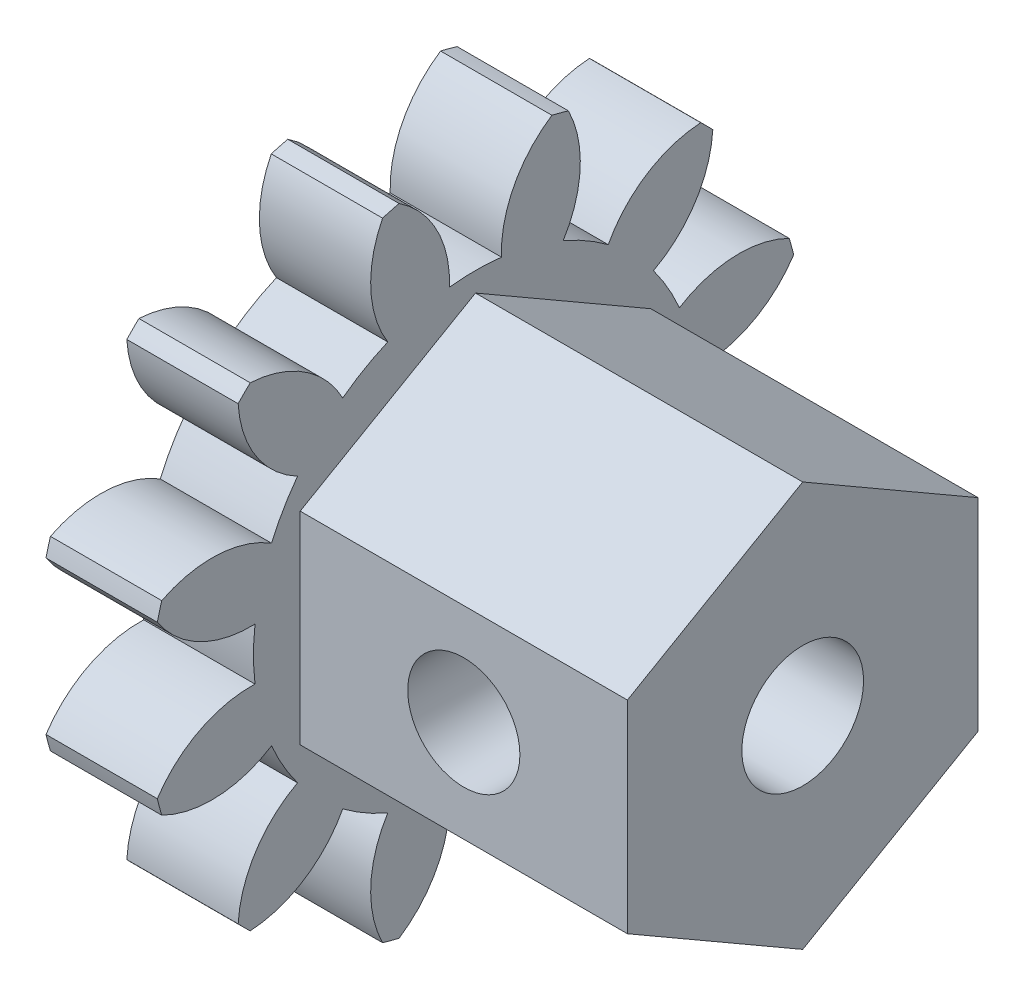
SolidWorks part; units mm, degrees
ref_plane "Plane1" through (0, 0, 0) normal (0, 0, 1) x (1, 0, 0)
ref_plane "Plane2" through (0, 0, 0) normal (0, 1, 0) x (1, 0, 0)
ref_plane "Plane3" through (0, 0, 0) normal (1, 0, 0) x (0, 0, -1)
sketch "HoldingSke" plane through (0, 0, 0) normal (0, 1, 0) x (1, 0, 0)
  line L0 (0, 0) -> (0.4891, -0.104)
  line L1 (-15, 0) -> (100, 0) construction
  line L2 (0, 0) -> (-2.1039, 2.3779)
  line L3 (0, 0) -> (-11.863, 4.5341)
  line L4 (0, 0) -> (8.4473, 1.7955)
  line L5 (0, 0) -> (-46.8476, -17.4728)
  line L6 (0, 0) -> (-3.9479, -2.6637)
  line L7 (-2.1039, 2.3779) -> (8.6586, 51.2059)
  line L8 (-76.2, 54.61) -> (-74.4, 54.61)
  line L9 (-71.009, 38.7566) -> (-53.1078, 45.2721)
  line L10 (-76.2, 71.12) -> (104.1128, 71.12)
  line L11 (0, 0) -> (-4.7625, 0)
  line L12 (-76.2, 101.6) -> (-76.133, 101.6)
  line L13 (24.9733, 27.94) -> (52.9518, 28.4284)
  line L14 (24.9733, 27.94) -> (24.9743, 27.94)
  line L15 (24.9733, 27.94) -> (100.4006, 29.5858)
  line L16 (-63.627, -2) -> (-12.827, -2)
  circle A0 centre (0, 0) radius 5
  circle A1 centre (0, 0) radius 9.499
  circle A2 centre (0, 0) radius 37.5
  circle A3 centre (0, 0) radius 5
  dimension "MHD" = 18.998
  dimension "Hub_dia" = 75
  dimension "Bore" = 10
  dimension "MBD" = 10
  dimension "Num_teeth" = 12
  dimension "Pitch_radius" = 180.3128
  dimension "Pitch" = 0.5
  dimension "Width" = 4.7625
  dimension "Overall_len" = 50
  dimension "Show_teeth" = 12
  dimension "Thickness" = 4.7625
  dimension "OAL" = 50.0001
  dimension "T_dim" = 1.8
  dimension "Ap" = 20
  dimension "H" = 19.05
  dimension "Backlash" = 0.067
  dimension "Addendum_fac" = 1
  dimension "Dedendum_fac" = 1.25
  dimension "Clearance_fac" = 0.25
  dimension "Dedendum_add" = 0.001
  dimension "Module" = 2
sketch "BasProSke" plane through (0, 0, 0) normal (0, 1, 0) x (1, 0, 0)
  line L0 (-10, 0) -> (60, 0) construction
  line L1 (0, 0) -> (0, 14)
  line L2 (0, 0) -> (4.7625, 0)
  line L3 (4.7625, 0) -> (4.7625, 14)
  line L4 (4.7625, 14) -> (0, 14)
  dimension "Diameter" = 28
  dimension "Thickness" = 4.7625
revolve "Base-Revolve" add sketch "BasProSke" angle 360 about L0
sketch "TooCutSke" plane through (0, 0, 0) normal (1, 0, 0) x (0, 0, -1)
  line L1 (0, 0) -> (0, 107) construction
  line L2 (0, 0) -> (-1.6834, 11.8813) construction
  line L3 (0, 0) -> (-6.1662, 23.0126) construction
  line L4 (-1.6834, 11.8813) -> (-3.0831, 11.5063) construction
  arc A0 (1.1119, 9.4337) -> (-1.1119, 9.4337) centre (0, 0) ccw
  arc A1 (3.2981, 13.6321) -> (-3.2981, 13.6321) centre (0, 0) ccw
  circle A2 centre (0, 0) radius 12 construction
  circle A3 centre (0, 0) radius 11.2763 construction
  arc A4 (-1.1119, 9.4337) -> (-3.2981, 13.6321) centre (-5.9089, 9.6042) ccw
  arc A5 (3.2981, 13.6321) -> (1.1119, 9.4337) centre (5.9089, 9.6042) ccw
  dimension "Root_dia" = 18.998
  dimension "Overcut_dia" = 28.0508
  dimension "Pitch_dia" = 24
  dimension "Base_dia" = 22.5526
  dimension "Flank_rad" = 4.8
  dimension "Half_ang" = 15
  dimension "Half_CT" = 1.4491
extrude "ToothCut" cut sketch "TooCutSke" along normal through all
fillet "Breaks" [suppressed] radius 0.04 tangent propagation no
fillet "RootFillets" [suppressed] radius 0.501
pattern_circular "TeethCuts" count 12 every 30 about axis through (-10, 0, 0) along (1, 0, 0) of "ToothCut", "RootFillets", "Breaks"
sketch "HubNeaOneSke" plane through (0, 0, 0) normal (-1, 0, 0) x (0, 0, 1)
  circle A0 centre (0, 0) radius 9.499
  dimension "Diameter" = 18.998
extrude "HubNearOne" [suppressed] add sketch "HubNeaOneSke" along normal blind 45.2376
sketch "HubNeaBotSke" plane through (0, 0, 0) normal (-1, 0, 0) x (0, 0, 1)
  circle A0 centre (0, 0) radius 9.499
  dimension "Diameter" = 18.998
extrude "HubNearBoth" [suppressed] add sketch "HubNeaBotSke" along normal blind 22.6188
ref_plane "FarPln" through (4.7625, 0, 0) normal (1, 0, 0) x (0, 0, -1)
sketch "HubFarSke" plane through (4.7625, 0, 0) normal (1, 0, 0) x (0, 0, -1)
  circle A0 centre (0, 0) radius 9.499
  dimension "Diameter" = 18.998
extrude "HubFar" [suppressed] add sketch "HubFarSke" along normal blind 22.6188
sketch "BorSke" plane through (0, 0, 0) normal (1, 0, 0) x (0, 0, -1)
  circle A0 centre (0, 0) radius 2.6035
  dimension "Diameter" = 5.207
extrude "Bore" cut sketch "BorSke" along normal mid plane 100.0001
sketch "KeySke" plane through (0, 0, 0) normal (1, 0, 0) x (0, 0, -1)
  line L0 (-2, 0) -> (-2, 6.8)
  line L1 (-2, 6.8) -> (2, 6.8)
  line L2 (2, 6.8) -> (2, 0)
  line L3 (0, 0) -> (0, 34) construction
  line L4 (-2, 0) -> (2, 0)
  dimension "Offset" = 6.8
  dimension "Width" = 4
extrude "Keyway" [suppressed] cut sketch "KeySke" along normal mid plane 100.0001
pattern_circular "Keyway2" [suppressed] count 2 every 90 about axis through (-10, 0, 0) along (1, 0, 0)
sketch "Sketch1" plane through (4.7625, 0, 0) normal (1, 0, 0) x (0, 0, -1)
  line L1 (0, 8.6603) -> (-7.5, 4.3301)
  line L2 (-7.5, 4.3301) -> (-7.5, -4.3301)
  line L3 (-7.5, -4.3301) -> (0, -8.6603)
  line L4 (0, -8.6603) -> (7.5, -4.3301)
  line L5 (7.5, -4.3301) -> (7.5, 4.3301)
  line L6 (7.5, 4.3301) -> (0, 8.6603)
  circle A0 centre (0, 0) radius 7.5 construction
  dimension "D1" = 15
extrude "Boss-Extrude1" add sketch "Sketch1" along normal blind 14
sketch "Sketch2" plane through (18.7625, 0, 0) normal (1, 0, 0) x (0, 0, -1)
  circle A0 centre (0, 0) radius 2.6035 construction
  circle A1 centre (0, 0) radius 2.6035
extrude "Cut-Extrude1" cut sketch "Sketch2" against normal through all
sketch "Sketch3" plane through (0, 0, 7.5) normal (0, 0, 1) x (1, 0, 0)
  line L0 (18.7625, 0) -> (4.7625, 0) construction
  line L3 (18.7625, 4.3301) -> (18.7625, -4.3301) construction
  line L4 (4.7625, -1.1119) -> (4.7625, 1.1119) construction
  circle A0 centre (11.7625, 0) radius 2.4
  dimension "D1" = 4.8
extrude "Cut-Extrude2" cut sketch "Sketch3" against normal through all
equation "' \"Module@HoldingSke\" = 6.35"
equation "' \"Num_teeth@HoldingSke\" = 12"
equation "' \"Ap@HoldingSke\" =  20"
equation "' \"Width@HoldingSke\" = 0.5 * 25.4"
equation "' \"Hub_dia@HoldingSke\"= 1 * 25.4"
equation "' \"Overall_len@HoldingSke\" = 1.0 * 25.4"
equation "' \"Bore@HoldingSke\" = 0.75 * 25.4"
equation "' \"T_dim@HoldingSke\" = 0.1 * 25.4"
equation "' \"Width@KeySke\" = 0.25 * 25.4"
equation "' \"Show_teeth@HoldingSke\" = 13"
equation "' \"Backlash@HoldingSke\" = 0.009 * 25.4"
equation "' \"Addendum_fac@HoldingSke\" = 1.0"
equation "' \"Dedendum_fac@HoldingSke\" = 1.25"
equation "' \"Dedendum_add@HoldingSke\" = 0.00005 * 25.4"
equation "' \"Clearance_fac@HoldingSke\" = 0.25"
equation "\"Pitch@HoldingSke\" = 1 / \"Module@HoldingSke\""
equation "\"Overcut_dia@TooCutSke\" = (\"Num_teeth@HoldingSke\" + 2 * \"Addendum_fac@HoldingSke\") / \"Pitch@HoldingSke\" + 0.002 * 25.4"
equation "\"Pitch_dia@TooCutSke\" = \"Num_teeth@HoldingSke\" / \"Pitch@HoldingSke\""
equation "\"Base_dia@TooCutSke\" = \"Num_teeth@HoldingSke\" / \"Pitch@HoldingSke\" * cos((\"Ap@HoldingSke\"  * 3.14159265 / 180))"
equation "\"Root_dia@TooCutSke\" = (\"Num_teeth@HoldingSke\" + 2) / \"Pitch@HoldingSke\" - 2 * (\"Addendum_fac@HoldingSke\" + \"Dedendum_fac@HoldingSke\") / \"Pitch@HoldingSke\" - \"Dedendum_add@HoldingSke\" * 2"
equation "\"Half_ang@TooCutSke\" = 180 / \"Num_teeth@HoldingSke\""
equation "\"Half_CT@TooCutSke\" = \"Num_teeth@HoldingSke\" / \"Pitch@HoldingSke\" * sin((3.14159265 / 2 / \"Num_teeth@HoldingSke\")) / 2 - 7 * \"Backlash@HoldingSke\" / 4"
equation "\"Flank_rad@TooCutSke\" = \"Num_teeth@HoldingSke\" / \"Pitch@HoldingSke\" / 5"
equation "\"Radius@RootFillets\" = \"Clearance_fac@HoldingSke\" / \"Pitch@HoldingSke\" + \"Dedendum_add@HoldingSke\""
equation "\"Break_rad@Breaks\" = 0.02 / \"Pitch@HoldingSke\""
equation "\"Thickness@HoldingSke\" = \"Width@HoldingSke\""
equation "\"OAL@HoldingSke\" = \"Thickness@HoldingSke\""
equation "\"MHD@HoldingSke\" = (\"Num_teeth@HoldingSke\" + 2) / \"Pitch@HoldingSke\" - 2 * (\"Addendum_fac@HoldingSke\" + \"Dedendum_fac@HoldingSke\")  / \"Pitch@HoldingSke\" - \"Dedendum_add@HoldingSke\" * 2"
equation "\"MBD@HoldingSke\" = (\"Num_teeth@HoldingSke\" + 2) / \"Pitch@HoldingSke\" - 2 * (\"Addendum_fac@HoldingSke\" + \"Dedendum_fac@HoldingSke\")  / \"Pitch@HoldingSke\" - \"Dedendum_add@HoldingSke\" * 2 - 0.002 * 25.4"
equation "\"MHD@HoldingSke\" = ((sgn( \"MHD@HoldingSke\" - \"Hub_dia@HoldingSke\" )-1)*( \"MHD@HoldingSke\" - \"Hub_dia@HoldingSke\" ))/-2+ \"Hub_dia@HoldingSke\""
equation "\"MBD@HoldingSke\" = ((sgn( \"MBD@HoldingSke\" - \"Bore@HoldingSke\" )-1)*( \"MBD@HoldingSke\" - \"Bore@HoldingSke\" ))/-2+ \"Bore@HoldingSke\""
equation "\"OAL@HoldingSke\" = ((sgn( \"OAL@HoldingSke\" - \"Overall_len@HoldingSke\" )+1)*( \"OAL@HoldingSke\" - \"Overall_len@HoldingSke\" ))/2 + \"Overall_len@HoldingSke\" + 0.000002 * 25.4"
equation "\"Num_teeth@TeethCuts\" = int( \"Show_teeth@HoldingSke\" ) + 1"
equation "\"Num_teeth@TeethCuts\" = ((sgn( \"Num_teeth@TeethCuts\" - \"Num_teeth@HoldingSke\" )-1)*( \"Num_teeth@TeethCuts\" - \"Num_teeth@HoldingSke\" ))/-2+ \"Num_teeth@HoldingSke\""
equation "\"Num_teeth@TeethCuts\" = ((sgn( \"Num_teeth@TeethCuts\" - 2.0)+1)*( \"Num_teeth@TeethCuts\" - 2.0))/2 +2.0"
equation "\"Angle@TeethCuts\" = 360.0 / \"Num_teeth@HoldingSke\""
equation "\"Diameter@BasProSke\" = (\"Num_teeth@HoldingSke\" + 2 * \"Addendum_fac@HoldingSke\") / \"Pitch@HoldingSke\""
equation "\"Thickness@BasProSke\"  = \"Thickness@HoldingSke\""
equation "' \"Fillet_rad@BasProSke\" =  \"Thickness@HoldingSke\" * 0.05"
equation "\"MHD@HoldingSke\" = ((sgn( \"MHD@HoldingSke\" - \"Root_dia@TooCutSke\" )-1)*( \"MHD@HoldingSke\" - \"Root_dia@TooCutSke\" ))/-2+ \"Root_dia@TooCutSke\""
equation "\"Diameter@HubNeaOneSke\" = \"MHD@HoldingSke\""
equation "\"Length@HubNearOne\" = \"OAL@HoldingSke\" - \"Thickness@BasProSke\""
equation "\"Diameter@HubNeaBotSke\" = \"MHD@HoldingSke\""
equation "\"Length@HubNearBoth\" = ( \"OAL@HoldingSke\" - \"Thickness@BasProSke\" ) / 2.0"
equation "\"Thickness@FarPln\" = \"Thickness@BasProSke\""
equation "\"Diameter@HubFarSke\" = \"MHD@HoldingSke\""
equation "\"Length@HubFar\" = ( \"OAL@HoldingSke\" - \"Thickness@BasProSke\" ) / 2.0"
equation "\"D1@Bore\" = \"OAL@HoldingSke\" * 2.0"
equation "\"D1@Keyway\" = \"OAL@HoldingSke\" * 2.0"
equation "\"Offset@KeySke\" = \"T_dim@HoldingSke\" + \"MBD@HoldingSke\" / 2.0"
